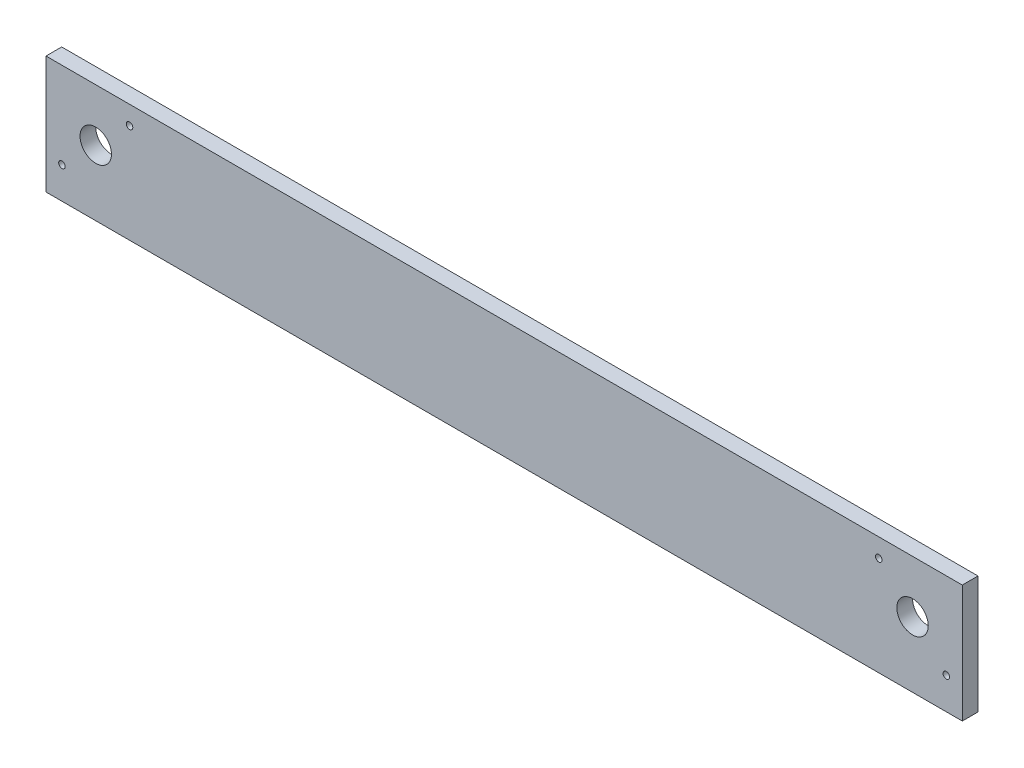
SolidWorks part; units mm, degrees
ref_plane "Alzado" through (0, 0, 0) normal (0, 0, 1) x (1, 0, 0)
ref_plane "Planta" through (0, 0, 0) normal (0, 1, 0) x (1, 0, 0)
ref_plane "Vista lateral" through (0, 0, 0) normal (1, 0, 0) x (0, 0, -1)
sketch "Croquis1" plane through (0, 0, 0) normal (0, 0, 1) x (1, 0, 0)
  line L1 (-350, -45) -> (0, -45)
  line L2 (-350, -45) -> (-350, 0)
  line L3 (-350, 0) -> (0, 0)
  line L4 (0, -45) -> (0, 0)
  dimension "D1" = 350
  dimension "D2" = 45
extrude "Saliente-Extruir1" add sketch "Croquis1" along normal blind 6 contours L3 L4 L1 L2
sketch "Croquis2" plane through (0, 0, 6) normal (0, 0, 1) x (1, 0, 0)
  line L0 (-350, -45) -> (-350, 0) construction
  line L1 (0, -45) -> (0, 0) construction
  line L2 (-350, -45) -> (0, -45) construction
  line L3 (-343.9047, -32.9047) -> (-318.0953, -7.0953) construction
  line L4 (-31.9047, -7.0953) -> (-6.0953, -32.9047) construction
  line L5 (-350, 0) -> (0, 0) construction
  circle A0 centre (-331, -20) radius 6
  circle A1 centre (-19, -20) radius 6
  circle A2 centre (-331, -20) radius 18.25 construction
  circle A4 centre (-318.0953, -7.0953) radius 1.25
  circle A5 centre (-343.9047, -32.9047) radius 1.25
  circle A6 centre (-19, -20) radius 18.25 construction
  circle A7 centre (-31.9047, -7.0953) radius 1.25
  circle A8 centre (-6.0953, -32.9047) radius 1.25
  dimension "D1" = 12
  dimension "D2" = 12
  dimension "D7" = 36.5
  dimension "D9" = 2.5
  dimension "D10" = 2.5
  dimension "D11" = 36.5
  dimension "D13" = 2.5
  dimension "D14" = 2.5
  dimension "D3" = 19
  dimension "D4" = 19
  dimension "D5" = 20
  dimension "D6" = 20
  dimension "D8" = 45
  dimension "D12" = 45
extrude "Cortar-Extruir1" cut sketch "Croquis2" against normal through all
